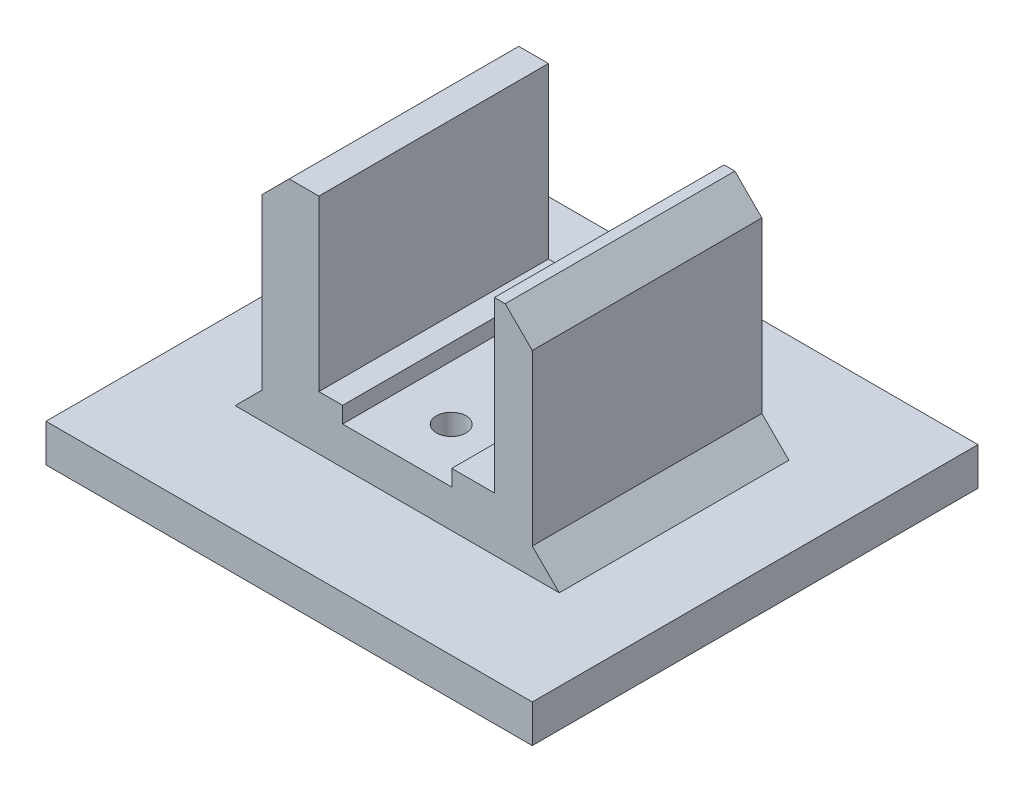
SolidWorks part; units mm, degrees
ref_plane "Front Plane" through (0, 0, 0) normal (0, 0, 1) x (1, 0, 0)
ref_plane "Top Plane" through (0, 0, 0) normal (0, 1, 0) x (1, 0, 0)
ref_plane "Right Plane" through (0, 0, 0) normal (1, 0, 0) x (0, 0, -1)
sketch "Sketch1" plane through (0, 0, 0) normal (1, 0, 0) x (0, 0, -1)
  line L1 (-25.5741, -19.2478) -> (-68.0741, -19.2478)
  line L2 (-25.5741, -19.2478) -> (-25.5741, -30.2478)
  line L3 (-25.5741, -30.2478) -> (-68.0741, -30.2478)
  line L4 (-68.0741, -19.2478) -> (-68.0741, -30.2478)
  dimension "D1" = 42.5
  dimension "D2" = 11
extrude "Boss-Extrude1" add sketch "Sketch1" along normal blind 50
sketch "Sketch2" plane through (0, 0, 0) normal (-1, 0, 0) x (0, 0, 1)
  line L0 (68.0741, -19.2478) -> (68.0741, -30.2478) construction
  line L1 (5.5741, -30.2478) -> (88.0741, -30.2478)
  line L2 (5.5741, -30.2478) -> (5.5741, -26.2478)
  line L3 (5.5741, -26.2478) -> (88.0741, -26.2478)
  line L4 (88.0741, -30.2478) -> (88.0741, -26.2478)
  line L5 (25.5741, -30.2478) -> (25.5741, -19.2478) construction
  dimension "D1" = 4
  dimension "D2" = 20
  dimension "D3" = 20
extrude "Boss-Extrude2" add sketch "Sketch2" along normal blind 20
sketch "Sketch3" plane through (0, 0, 0) normal (1, 0, 0) x (0, 0, -1)
  line L1 (-88.0741, -30.2478) -> (-5.5741, -30.2478)
  line L2 (-88.0741, -30.2478) -> (-88.0741, -26.2478)
  line L3 (-88.0741, -26.2478) -> (-5.5741, -26.2478)
  line L4 (-5.5741, -30.2478) -> (-5.5741, -26.2478)
extrude "Boss-Extrude3" add sketch "Sketch3" along normal blind 70
sketch "Sketch4" plane through (0, 0, 68.0741) normal (0, 0, 1) x (1, 0, 0)
  line L0 (50, -19.2478) -> (0, -19.2478) construction
  line L1 (10.5, -19.2478) -> (0, -19.2478)
  line L2 (10.5, -19.2478) -> (10.5, 15.0934)
  line L3 (10.5, 15.0934) -> (0, 15.0934)
  line L4 (0, -19.2478) -> (0, 15.0934)
  line L5 (0, -19.2478) -> (0, -26.2478) construction
  line L6 (50, -19.2478) -> (43, -19.2478)
  line L7 (50, -19.2478) -> (50, 15.0934)
  line L8 (50, 15.0934) -> (43, 15.0934)
  line L9 (43, -19.2478) -> (43, 15.0934)
  point P11 (0, -19.2478)
  point P14 (50, -19.2478)
  dimension "D1" = 10.5
  dimension "D2" = 7
extrude "Boss-Extrude4" add sketch "Sketch4" against normal up to surface (42.5 mm away) up to face at (25, -22.7478, 25.5741)
chamfer "Chamfer1" distance 5 angle 45 2 edges at (0, -26.2478, 46.8241) (50, -26.2478, 46.8241)
sketch "Sketch5" plane through (0, -30.2478, 0) normal (0, -1, 0) x (1, 0, 0)
  line L1 (-20, 5.5741) -> (70, 5.5741)
  line L2 (-20, 5.5741) -> (-20, 88.0741)
  line L3 (-20, 88.0741) -> (70, 88.0741)
  line L4 (70, 5.5741) -> (70, 88.0741)
extrude "Boss-Extrude5" add sketch "Sketch5" along normal blind 3
sketch "Sketch6" plane through (0, -19.2478, 0) normal (0, 1, 0) x (1, 0, 0)
  circle A0 centre (25, -36.0741) radius 2.75
  circle A1 centre (25, -58.0741) radius 2.75
  dimension "D1" = 5.5
  dimension "D2" = 5.5
extrude "Cut-Extrude1" cut sketch "Sketch6" against normal through all
sketch "Sketch7" plane through (0, -19.2478, 0) normal (0, 1, 0) x (1, 0, 0)
  line L0 (43, -25.5741) -> (10.5, -25.5741) construction
  line L1 (43, -68.0741) -> (35.1, -68.0741)
  line L2 (43, -68.0741) -> (43, -25.5741)
  line L3 (43, -25.5741) -> (35.1, -25.5741)
  line L4 (35.1, -68.0741) -> (35.1, -25.5741)
  line L5 (35, -68.5741) -> (35, -47.5741) construction
  line L6 (10.5, -68.0741) -> (14.9, -68.0741)
  line L7 (10.5, -68.0741) -> (10.5, -25.5741)
  line L8 (10.5, -25.5741) -> (14.9, -25.5741)
  line L9 (14.9, -68.0741) -> (14.9, -25.5741)
  line L10 (15, -68.5741) -> (15, -47.5741) construction
  dimension "D1" = 0.1
  dimension "D2" = 0.1
extrude "Boss-Extrude6" add sketch "Sketch7" along normal blind 3
chamfer "Chamfer2" distance 5 angle 45 2 edges at (50, 15.0934, 46.8241) (0, 15.0934, 46.8241)
